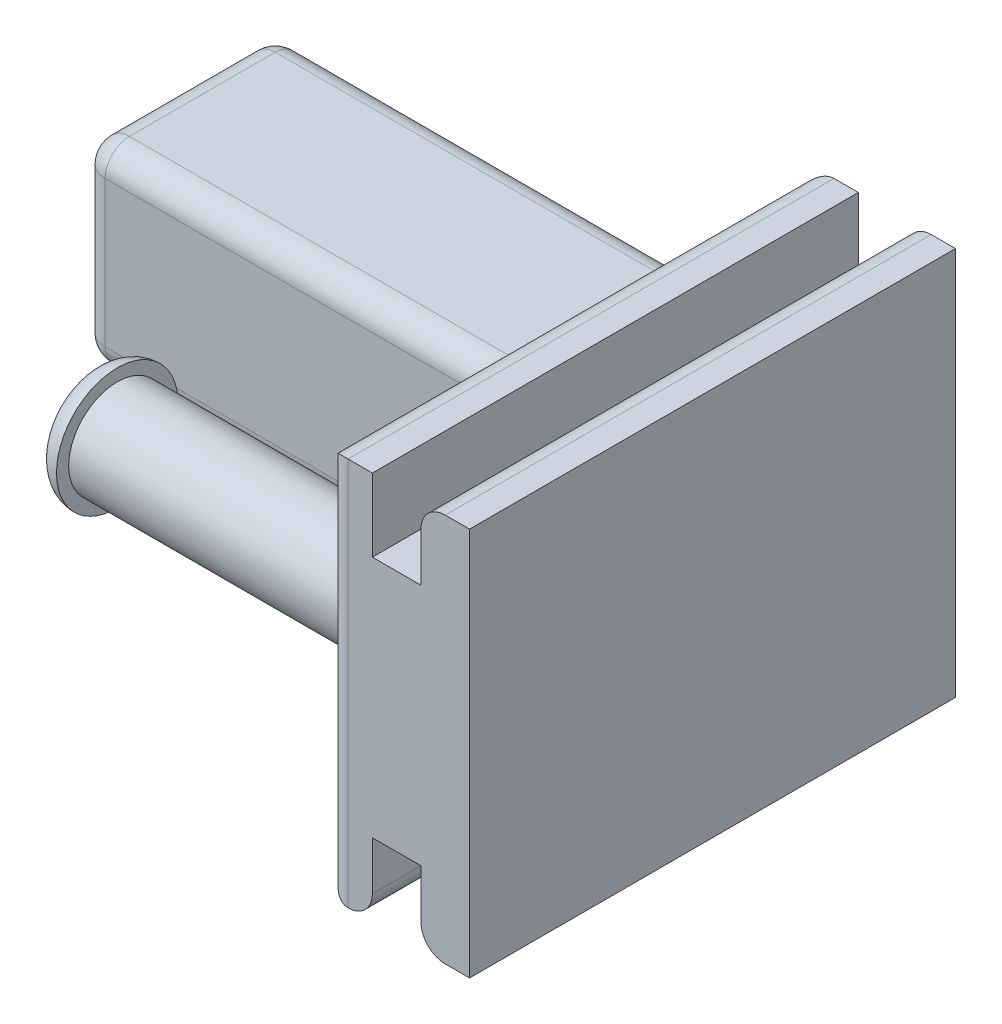
SolidWorks part; units mm, degrees
ref_plane "Front Plane" through (0, 0, 0) normal (0, 0, 1) x (1, 0, 0)
ref_plane "Top Plane" through (0, 0, 0) normal (0, 1, 0) x (1, 0, 0)
ref_plane "Right Plane" through (0, 0, 0) normal (1, 0, 0) x (0, 0, -1)
sketch "Sketch1" plane through (0, 0, 0) normal (0, 0, 1) x (1, 0, 0)
  line L0 (0, 5) -> (0, -5) construction
  line L1 (-1, -5) -> (1, -5)
  line L2 (-1, -5) -> (-1, 5)
  line L3 (-1, 5) -> (1, 5)
  line L4 (1, -5) -> (1, 5)
  line L5 (-1, -5) -> (1, 5) construction
  line L6 (-1, 5) -> (1, -5) construction
  line L7 (-3, -8) -> (-1, -8)
  line L8 (-3, -8) -> (-3, 8)
  line L9 (-3, 8) -> (-1, 8)
  line L10 (-1, -8) -> (-1, 8)
  line L11 (-3, -8) -> (-1, 8) construction
  line L12 (-3, 8) -> (-1, -8) construction
  line L13 (3, 8) -> (1, 8)
  line L14 (1, -8) -> (1, 8)
  line L15 (3, -8) -> (1, -8)
  line L16 (3, -8) -> (3, 8)
  point P0 (0, 0)
  point P5 (-2, 0)
  dimension "D1" = 10
  dimension "D2" = 2
  dimension "D3" = 2
  dimension "D4" = 0
  dimension "D5" = 5
  dimension "D6" = 16
extrude "Boss-Extrude1" add sketch "Sketch1" along normal blind 20 contours L7 L10 L2 L9 L8 | L1 L4 L3 L2 | L15 L16 L13 L14 L4 region at (0, 0, 0) region at (-2, 0, 0) region at (2, 0, 0)
sketch "Sketch2" plane through (-3, 0, 0) normal (-1, 0, 0) x (0, 0, 1)
  line L0 (20, 8) -> (0, 8) construction
  line L1 (20, -8) -> (20, 8) construction
  circle A0 centre (16, 0) radius 2
  dimension "D1" = 4
  dimension "D2" = 8
  dimension "D3" = 4
extrude "Boss-Extrude2" add sketch "Sketch2" along normal blind 13.5
sketch "Sketch3" plane through (-16.5, 0, 0) normal (-1, 0, 0) x (0, 0, 1)
  circle A0 centre (16, 0) radius 2.5
  dimension "D1" = 5
extrude "Boss-Extrude3" add sketch "Sketch3" against normal blind 1
sketch "Sketch4" plane through (-3, 0, 0) normal (-1, 0, 0) x (0, 0, 1)
  line L0 (0, -8) -> (0, 8) construction
  line L1 (2, -4) -> (10, -4)
  line L2 (2, -4) -> (2, 4)
  line L3 (2, 4) -> (10, 4)
  line L4 (10, -4) -> (10, 4)
  line L5 (2, -4) -> (10, 4) construction
  line L6 (2, 4) -> (10, -4) construction
  line L7 (20, -8) -> (0, -8) construction
  point P0 (6, 0)
  dimension "D1" = 8
  dimension "D2" = 6
  dimension "D3" = 8
  dimension "D4" = 8
extrude "Boss-Extrude4" add sketch "Sketch4" along normal blind 20
fillet "Fillet1" radius 1 21 edges at (-3, -4, 6) (-13, 4, 2) (-23, 0, 2) (-13, -4, 2) (-3, 0, 2) (-3, 0, 18) (-13, 4, 10) (-3, 4, 6) (-3, 0, 10) (-13, -4, 10) (1, -8, 10) (-1, -8, 10) (1, 8, 10) (-16.5, 0, 18.5) (-23, -4, 6) (-23, 4, 6) (-23, 0, 10) (-3, 8, 10) (-3, 0, 20) (-3, -8, 10) (-3, 0, 0)
